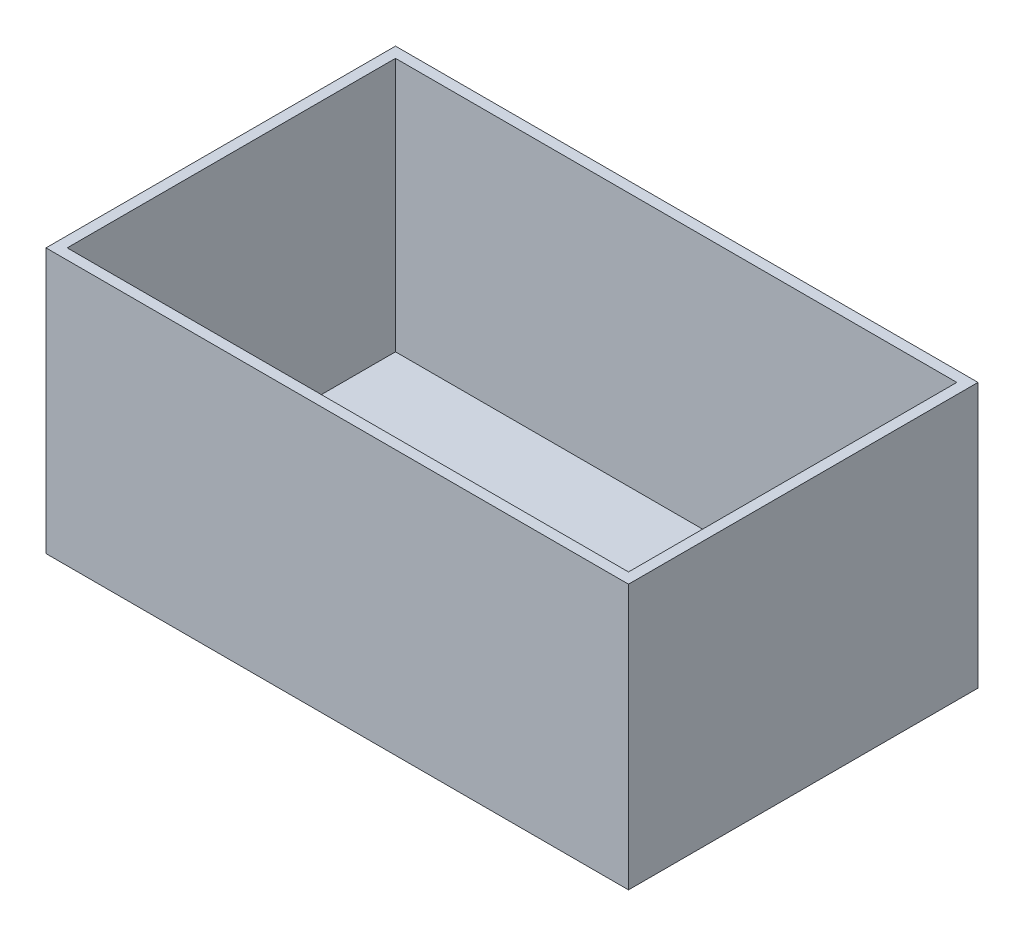
SolidWorks part; units mm, degrees
material "Glass"
ref_plane "Front" through (0, 0, 0) normal (0, 0, 1) x (1, 0, 0)
ref_plane "Top" through (0, 0, 0) normal (0, 1, 0) x (1, 0, 0)
ref_plane "Right" through (0, 0, 0) normal (1, 0, 0) x (0, 0, -1)
sketch "Sketch1" plane through (0, 0, 0) normal (0, 1, 0) x (1, 0, 0)
  line L0 (-349.25, -209.55) -> (-349.25, 209.55)
  line L1 (336.55, -196.85) -> (-336.55, -196.85)
  line L2 (336.55, -196.85) -> (336.55, 196.85)
  line L3 (336.55, 196.85) -> (-336.55, 196.85)
  line L4 (-336.55, -196.85) -> (-336.55, 196.85)
  line L5 (336.55, -196.85) -> (-336.55, 196.85) construction
  line L6 (336.55, 196.85) -> (-336.55, -196.85) construction
  line L7 (349.25, 209.55) -> (-349.25, 209.55)
  line L8 (349.25, -209.55) -> (349.25, 209.55)
  line L9 (349.25, -209.55) -> (-349.25, -209.55)
  point P0 (0, 0)
  dimension "D2" = 698.5
  dimension "D3" = 419.1
  dimension "D1" = 12.7
extrude "Boss-Extrude1" add sketch "Sketch1" against normal blind 12.7 contours L0 L7 L8 L9
extrude "Boss-Extrude2" add sketch "Sketch1<3>" along normal blind 304.8
sketch "Sketch1<3>" plane through (0, 0, 0) normal (0, 1, 0) x (1, 0, 0) same geometry as "Sketch1"
